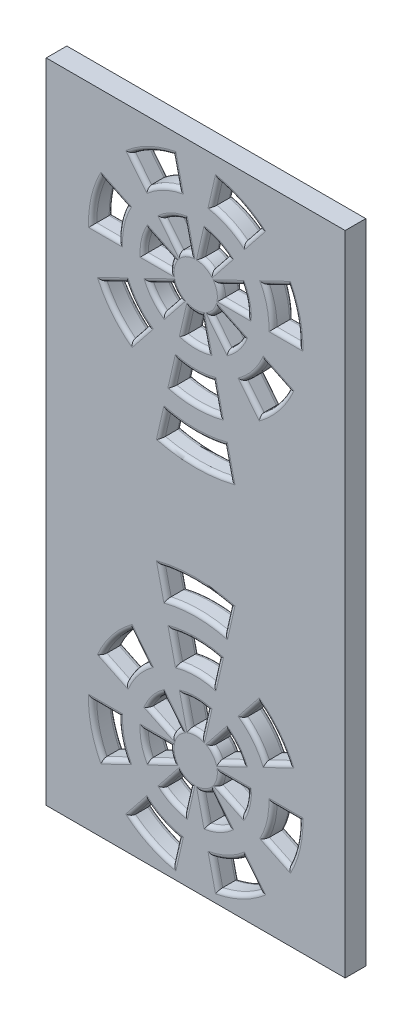
SolidWorks part; units mm, degrees
ref_plane "Front Plane" through (0, 0, 0) normal (0, 0, 1) x (1, 0, 0)
ref_plane "Top Plane" through (0, 0, 0) normal (0, 1, 0) x (1, 0, 0)
ref_plane "Right Plane" through (0, 0, 0) normal (1, 0, 0) x (0, 0, -1)
sketch "Sketch1" plane through (0, 0, 0) normal (0, 1, 0) x (1, 0, 0)
  line L1 (-19.5, 77.5) -> (19.5, 77.5)
  line L2 (-19.5, 77.5) -> (-19.5, -77.5)
  line L3 (-19.5, -77.5) -> (19.5, -77.5)
  line L4 (19.5, 77.5) -> (19.5, -77.5)
  line L5 (-19.5, 77.5) -> (19.5, -77.5) construction
  line L6 (-19.5, -77.5) -> (19.5, 77.5) construction
  point P0 (0, 0)
  dimension "D1" = 39
  dimension "D2" = 155
extrude "Boss-Extrude1" add sketch "Sketch1" along normal blind 2
sketch "Sketch2" plane through (0, 2, 0) normal (0, 1, 0) x (1, 0, 0)
  line L0 (-17.5, -75.5) -> (-17.5, -77.5)
  line L1 (-19.5, 77.5) -> (19.5, 77.5)
  line L2 (-19.5, 77.5) -> (-19.5, -77.5)
  line L3 (-19.5, -77.5) -> (19.5, -77.5)
  line L4 (19.5, 77.5) -> (19.5, -77.5)
  line L5 (-17.5, 75.5) -> (17.5, 75.5)
  line L6 (-17.5, 75.5) -> (-17.5, -75.5)
  line L7 (-17.5, -75.5) -> (17.5, -75.5)
  line L8 (17.5, 75.5) -> (17.5, -75.5)
  line L9 (-17.5, 75.5) -> (17.5, -75.5) construction
  line L10 (-17.5, -75.5) -> (17.5, 75.5) construction
  line L11 (17.5, -75.5) -> (17.5, -77.5)
  point P6 (0, 0)
  line M9 (19.5, -77.5) -> (19.5, 77.5)
  line M10 (19.5, 77.5) -> (-19.5, 77.5)
  line M11 (-19.5, 77.5) -> (-19.5, -77.5)
  line M12 (-19.5, -77.5) -> (19.5, -77.5)
  dimension "D1" = 2
  dimension "D2" = 2
extrude "Boss-Extrude2" add sketch "Sketch2" along normal blind 78 contours L8 L11 L3 L0 L6 L5 M9 M10 M11 M12 region at (-19.0983, 2, 76.5)
sketch "Sketch3" plane through (0, 2, 0) normal (0, 1, 0) x (1, 0, 0)
  line L0 (-17.5, 75.5) -> (-17.5, -77.5) construction
  line L1 (-17.5, -77.5) -> (-15.5, -77.5)
  line L2 (-17.5, -77.5) -> (-17.5, -75.5)
  line L3 (-17.5, -75.5) -> (-15.5, -75.5)
  line L4 (-15.5, -77.5) -> (-15.5, -75.5)
  line L5 (-17.5, -73.3) -> (-15.5, -73.3)
  line L6 (-17.5, -73.3) -> (-17.5, -71.3)
  line L7 (-17.5, -71.3) -> (-15.5, -71.3)
  line L8 (-15.5, -73.3) -> (-15.5, -71.3)
  line L9 (17.5, 75.5) -> (17.5, -77.5) construction
  line L10 (17.5, -77.5) -> (15.5, -77.5)
  line L11 (17.5, -77.5) -> (17.5, -75.5)
  line L12 (17.5, -75.5) -> (15.5, -75.5)
  line L13 (15.5, -77.5) -> (15.5, -75.5)
  line L14 (17.5, -73.3) -> (15.5, -73.3)
  line L15 (17.5, -73.3) -> (17.5, -71.3)
  line L16 (17.5, -71.3) -> (15.5, -71.3)
  line L17 (15.5, -73.3) -> (15.5, -71.3)
  line L18 (15.5, -75.5) -> (15.5, -73.3) construction
  line L19 (-15.5, -73.3) -> (15.5, -73.3) construction
  line L20 (-15.5, -75.5) -> (-15.5, -73.3) construction
  line L21 (-15.5, -75.5) -> (15.5, -75.5) construction
  line L22 (15.5, -71.3) -> (-15.5, -71.3) construction
  dimension "D1" = 2
  dimension "D2" = 2
  dimension "D3" = 2.2
  dimension "D4" = 2
extrude "Boss-Extrude3" add sketch "Sketch3" along normal up to surface (78 mm away) up to face at (0, 80, 0.5)
sketch "Sketch4" plane through (0, 0, -75.5) normal (0, 0, 1) x (1, 0, 0)
  line L0 (-17.5, 80) -> (-15.5, 80)
  line L1 (-17.5, 80) -> (17.5, 80) construction
  line L2 (-15.5, 80) -> (-15.5, 78)
  line L3 (-15.5, 78) -> (-17.5, 78)
  line L5 (-17.5, 78) -> (-17.5, 80)
  line L7 (-17.5, 80) -> (-17.5, 2) construction
  line L8 (-15.5, 73.8) -> (-17.5, 71.8)
  line L9 (-17.5, 71.8) -> (-17.5, 75.8)
  line L10 (-15.5, 73.8) -> (-15.5, 75.8)
  line L11 (-15.5, 75.8) -> (-17.5, 75.8)
  line L12 (0, 0) -> (0, 80) construction
  line L13 (15.5, 75.8) -> (17.5, 75.8)
  line L14 (15.5, 73.8) -> (15.5, 75.8)
  line L15 (17.5, 71.8) -> (17.5, 75.8)
  line L16 (15.5, 73.8) -> (17.5, 71.8)
  line L17 (17.5, 78) -> (17.5, 80)
  line L18 (15.5, 78) -> (17.5, 78)
  line L19 (15.5, 80) -> (15.5, 78)
  line L20 (17.5, 80) -> (15.5, 80)
  dimension "D1" = 2
  dimension "D2" = 2
  dimension "D3" = 45
  dimension "D4" = 2.2
  dimension "D5" = 2
extrude "Boss-Extrude4" add sketch "Sketch4" along normal up to surface (153 mm away) up to face at (0, 40.5, 77.5)
sketch "Sketch5" plane through (0, 2, 0) normal (0, 1, 0) x (1, 0, 0)
  line L1 (-15.5, -77.5) -> (15.5, -77.5)
  line L2 (-15.5, -77.5) -> (-15.5, -75.5)
  line L3 (-15.5, -75.5) -> (15.5, -75.5)
  line L4 (15.5, -77.5) -> (15.5, -75.5)
  line L5 (-15.5, -71.3) -> (15.5, -71.3)
  line L6 (-15.5, -71.3) -> (-15.5, -73.3)
  line L7 (-15.5, -73.3) -> (15.5, -73.3)
  line L8 (15.5, -71.3) -> (15.5, -73.3)
sketch "Sketch6" plane through (0, 0, -75.5) normal (0, 0, 1) x (1, 0, 0)
  line L0 (-17.5, 78) -> (-15.5, 78) construction
  line L1 (-17.5, 78) -> (17.5, 78)
  line L2 (-17.5, 78) -> (-17.5, 75.8)
  line L3 (-17.5, 75.8) -> (17.5, 75.8)
  line L4 (17.5, 78) -> (17.5, 75.8)
  line L5 (-17.5, 78) -> (-17.5, 75.8) construction
  line L6 (-15.5, 75.8) -> (-17.5, 75.8) construction
extrude "Cut-Extrude1" cut sketch "Sketch6" along normal through all
sketch "Sketch7" plane through (0, 2, 0) normal (0, 1, 0) x (1, 0, 0)
  line L1 (-17.5, -75.5) -> (17.5, -75.5)
  line L2 (-17.5, -75.5) -> (-17.5, -73.3)
  line L3 (-17.5, -73.3) -> (17.5, -73.3)
  line L4 (17.5, -75.5) -> (17.5, -73.3)
extrude "Cut-Extrude2" cut sketch "Sketch7" along normal through all
extrude "Boss-Extrude5" add sketch "Sketch5" along normal blind 2
sketch "Sketch8" plane through (0, 0, 0) normal (1, 0, 0) x (0, 0, -1)
  line L0 (75.5, 80) -> (73.5, 80)
  line L1 (-73.3, 80) -> (75.5, 80) construction
  line L2 (73.5, 80) -> (73.5, 78)
  line L3 (-73.3, 78) -> (75.5, 78) construction
  line L4 (73.5, 78) -> (75.5, 78)
  line L5 (75.5, 78) -> (75.5, 80)
  line L6 (75.5, 75.8) -> (73.5, 75.8)
  line L7 (-73.3, 75.8) -> (75.5, 75.8) construction
  line L8 (73.5, 75.8) -> (73.5, 73.8)
  line L9 (-71.3, 73.8) -> (75.5, 73.8) construction
  line L10 (73.5, 73.8) -> (75.5, 71.8)
  line L11 (75.5, 71.8) -> (75.5, 75.8)
  dimension "D1" = 2
extrude "Boss-Extrude6" add sketch "Sketch8" along normal up to surface and the other way up to surface up to face at (17.5, 36.9, -2.1) other way up to face at (-17.5, 36.9, -2.1)
sketch "Sketch10" plane through (-17.5, 0, 0) normal (1, 0, 0) x (0, 0, -1)
  line L1 (-75.5, 75.8) -> (-77.5, 75.8)
  line L2 (-75.5, 75.8) -> (-75.5, 78)
  line L3 (-75.5, 78) -> (-77.5, 78)
  line L4 (-77.5, 75.8) -> (-77.5, 78)
  line L5 (-73.3, 80) -> (-75.5, 80)
  line L6 (-73.3, 80) -> (-73.3, 78)
  line L7 (-73.3, 78) -> (-75.5, 78)
  line L8 (-75.5, 80) -> (-75.5, 78)
  line M1 (-75.5, 80) -> (-75.5, 78)
  line M2 (-75.5, 78) -> (-77.5, 78)
  line M3 (-77.5, 78) -> (-77.5, 75.8)
  line M4 (-77.5, 75.8) -> (-75.5, 75.8)
  line M11 (-73.3, 78) -> (-73.3, 80)
  line M12 (-73.3, 80) -> (-75.5, 80)
extrude "Boss-Extrude8" add sketch "Sketch10" along normal up to surface (2 mm away) contours L2 M4 M2 M3 | L7 M11 M12 M1 region at (-17.5, 79, 74.4) region at (-17.5, 76.9, 76.5) up to face at (-15.5, 79, -0.1)
sketch "Sketch11" plane through (17.5, 0, 0) normal (-1, 0, 0) x (0, 0, 1)
  line L1 (75.5, 75.8) -> (77.5, 75.8)
  line L2 (75.5, 75.8) -> (75.5, 78)
  line L3 (75.5, 78) -> (77.5, 78)
  line L4 (77.5, 75.8) -> (77.5, 78)
  line L5 (73.3, 80) -> (75.5, 80)
  line L6 (73.3, 80) -> (73.3, 78)
  line L7 (73.3, 78) -> (75.5, 78)
  line L8 (75.5, 80) -> (75.5, 78)
  line M2 (75.5, 75.8) -> (77.5, 75.8)
  line M3 (77.5, 75.8) -> (77.5, 78)
  line M4 (77.5, 78) -> (75.5, 78)
  line M5 (75.5, 78) -> (75.5, 80)
  line M6 (75.5, 80) -> (73.3, 80)
  line M7 (73.3, 80) -> (73.3, 78)
extrude "Boss-Extrude9" add sketch "Sketch11" along normal up to surface (2 mm away) contours L2 M2 M3 M4 | L7 M7 M5 M6 region at (17.5, 76.9, 76.5) region at (17.5, 79, 74.4) up to face at (15.5, 79, -0.1)
fillet "Fillet2" radius 2.5 17 edges at (-17.5, 36.9, 71.3) (17.5, 36.9, 71.3) (19.5, 40, 77.5) (-19.5, 40, 77.5) (-19.5, 40, -77.5) (-17.5, 36.9, -75.5) (17.5, 36.9, -75.5) (19.5, 40, -77.5) (-19.5, 80, 0) (0, 80, -77.5) (19.5, 80, 0) (0, 0, -77.5) (0, 0, 77.5) (-19.5, 0, 0) (19.5, 0, 0) (-17.5, 80, 77.5) (17.5, 80, 77.5)
sketch "Sketch13" plane through (0, 0, -77.5) normal (0, 0, -1) x (-1, 0, 0)
  line L0 (15.5, 77.5) -> (15.5, 4) construction
  line L1 (-15.5, 7) -> (15.5, 7)
  line L2 (-15.5, 7) -> (-15.5, 4)
  line L3 (-15.5, 4) -> (15.5, 4)
  line L4 (15.5, 7) -> (15.5, 4)
  dimension "D1" = 3
sketch "Sketch14" plane through (0, 0, -75.5) normal (0, 0, 1) x (1, 0, 0)
  line L1 (-18.25, 9) -> (18.25, 9)
  line L2 (-18.25, 9) -> (-18.25, 1.25)
  line L3 (-18.25, 1.25) -> (18.25, 1.25)
  line L4 (18.25, 9) -> (18.25, 1.25)
  line L5 (15.5, 7) -> (-15.5, 7) construction
  line L7 (17, 0) -> (17, 2.5) construction
  line L8 (19.5, 2.5) -> (17, 2.5) construction
  line L10 (-19.5, 2.5) -> (-17, 2.5) construction
  point P20 (17, 1.25)
  point P23 (18.25, 2.5)
  point P26 (-18.25, 2.5)
  dimension "D1" = 2
extrude "Boss-Extrude10" add sketch "Sketch14" along normal blind 2
extrude "Cut-Extrude4" cut sketch "Sketch13" against normal blind 2
fillet "Fillet3" radius 2 1 edges at (0, 9, -73.5)
fillet "Fillet4" radius 0.5 12 edges at (0, 4, -77.5) (0, 7, -77.5) (15.5, 7, -76.5) (15.5, 4, -76.5) (15.5, 5.5, -77.5) (-15.5, 4, -76.5) (-15.5, 7, -76.5) (-15.5, 5.5, -77.5) (0, 7, -75.5) (-15.5, 5.5, -75.5) (0, 4, -75.5) (15.5, 5.5, -75.5)
sketch "Sketch15" plane through (0, 0, 0) normal (0, -1, 0) x (1, 0, 0)
  line L0 (0, 77.5) -> (0, 0) construction
  line L1 (-17, 77.5) -> (17, 77.5) construction
  line L2 (0, 0) -> (0, -77.5) construction
  line L4 (17, -77.5) -> (-17, -77.5) construction
  circle A0 centre (0, 38.75) radius 5.1
  circle A1 centre (0, -38.75) radius 5.1
  dimension "D1" = 10.2
extrude "Cut-Extrude5" cut sketch "Sketch15" against normal through all
sketch "Sketch16" plane through (0, 2, 0) normal (0, 1, 0) x (1, 0, 0)
  circle A0 centre (0, 38.75) radius 7.1
  circle A1 centre (0, -38.75) radius 7.1
  circle A2 centre (0, 38.75) radius 5.1 construction
  dimension "D1" = 2
extrude "Boss-Extrude11" add sketch "Sketch16" along normal blind 1
fillet "Fillet5" radius 0.5 4 edges at (0, 2, 45.85) (0, 2, -31.65) (0, 3, 45.85) (0, 3, -31.65)
sketch "Sketch12" plane through (0, 0, -75.5) normal (0, 0, 1) x (1, 0, 0)
  line L0 (0, 0) -> (0, 40) construction
  line L2 (0, 20) -> (-20, 20)
  line L3 (0, 20) -> (-18.0194, 11.3223)
  line L4 (0, 20) -> (-12.4698, 4.3634)
  line L5 (0, 20) -> (-4.4504, 0.5014)
  line L6 (0, 20) -> (4.4504, 0.5014)
  line L7 (0, 20) -> (12.4698, 4.3634)
  line L8 (0, 20) -> (18.0194, 11.3223)
  line L9 (0, 20) -> (20, 20)
  line L10 (0, 20) -> (18.0194, 28.6777)
  line L11 (0, 20) -> (12.4698, 35.6366)
  line L12 (0, 20) -> (4.4504, 39.4986)
  line L13 (0, 20) -> (-4.4504, 39.4986)
  line L14 (0, 20) -> (-12.4698, 35.6366)
  line L15 (0, 20) -> (-18.0194, 28.6777)
  line L16 (0, 40) -> (0, 80) construction
  line L17 (15.5, 80) -> (-15.5, 80) construction
  circle A0 centre (0, 20) radius 10
  circle A1 centre (0, 20) radius 7.5
  circle A2 centre (0, 20) radius 5
  circle A3 centre (0, 20) radius 2.5
  circle A4 centre (0, 20) radius 12.5
  circle A5 centre (0, 20) radius 15
  circle A6 centre (0, 20) radius 17.5
  circle A7 centre (0, 20) radius 20
  point P26 (0, 20)
  dimension "D1" = 20
  dimension "D2" = 2.5
  dimension "D3" = 2.5
  dimension "D4" = 2.5
  dimension "D6" = 2.5
  dimension "D7" = 2.5
  dimension "D8" = 2.5
  dimension "D9" = 2.5
  dimension "D5" = 14
extrude "Cut-Extrude6" cut sketch "Sketch12" against normal blind 10 contours A3 L12 A2 L13 | A3 L10 A2 L11 | A3 L8 A2 L9 | A3 L6 A2 L7 | A3 L4 A2 L5 | A3 L2 A2 L3 | A3 L14 A2 L15 | A1 L12 A0 L13 | A1 L10 A0 L11 | A1 L8 A0 L9 | A1 L6 A0 L7 | A1 L4 A0 L5 | A1 L2 A0 L3 | A1 L14 A0 L15 | L12 A5 L13 A4 region at (-3.7596, 19.1419, -75.5) region at (-1.6732, 16.5256, -75.5) region at (1.6732, 16.5256, -75.5) region at (3.7596, 19.1419, -75.5) region at (3.015, 22.4044, -75.5) region at (0, 23.8563, -75.5) region at (-3.015, 22.4044, -75.5) region at (-8.5168, 18.0561, -75.5) region at (-3.7903, 12.1293, -75.5) region at (3.7903, 12.1293, -75.5) region at (8.5168, 18.0561, -75.5) region at (6.8299, 25.4467, -75.5) region at (0, 28.7358, -75.5) region at (-6.8299, 25.4467, -75.5) region at (0, 33.6725, -75.5)
fillet "Fillet6" radius 0.4 120 edges at (-3.3786, 18.3729, -77.5) (-4.8746, 18.8874, -77.5) (-3.75, 20, -77.5) (-2.4373, 19.4437, -77.5) (0, 30, -77.5) (1.9471, 28.5306, -77.5) (0, 27.5, -77.5) (2.3381, 22.9319, -77.5) (3.9092, 23.1174, -77.5) (2.3381, 17.0681, -77.5) (1.0847, 17.7476, -77.5) (8.75, 20, -77.5) (9.7493, 17.7748, -77.5) (7.8835, 16.2035, -77.5) (7.312, 18.3311, -77.5) (-4.3388, 10.9903, -77.5) (-3.2541, 13.2427, -77.5) (-7.8835, 23.7965, -77.5) (-5.4555, 26.841, -77.5) (-5.8637, 24.6762, -77.5) (0, 35, -77.5) (3.0597, 33.4053, -77.5) (0, 32.5, -77.5) (0.8345, 23.656, -77.5) (0, 22.5, -77.5) (-9.7493, 17.7748, -77.5) (5.4555, 13.159, -77.5) (4.3388, 10.9903, -77.5) (1.9471, 11.4694, -77.5) (-0.8345, 16.344, -77.5) (-2.1694, 15.4952, -77.5) (-2.3381, 17.0681, -77.5) (-1.0847, 17.7476, -77.5) (3.75, 20, -77.5) (4.8746, 18.8874, -77.5) (3.3786, 18.3729, -77.5) (2.4373, 19.4437, -77.5) (7.8183, 26.2349, -77.5) (-3.9092, 23.1174, -77.5) (-1.9546, 21.5587, -77.5) (-3.0597, 33.4053, -77.5) (-3.3786, 18.3729, -75.5) (-2.4373, 19.4437, -75.5) (0, 30, -75.5) (-1.9471, 28.5306, -75.5) (0, 27.5, -75.5) (3.3786, 21.6271, -75.5) (1.9546, 21.5587, -75.5) (0.8345, 16.344, -75.5) (2.1694, 15.4952, -75.5) (2.3381, 17.0681, -75.5) (7.8835, 16.2035, -75.5) (9.7493, 17.7748, -75.5) (7.312, 18.3311, -75.5) (-4.3388, 10.9903, -75.5) (-7.8183, 26.2349, -75.5) (-7.8835, 23.7965, -75.5) (-5.8637, 24.6762, -75.5) (0, 32.5, -75.5) (3.0597, 33.4053, -75.5) (0, 35, -75.5) (0.8345, 23.656, -75.5) (0, 25, -75.5) (-0.8345, 23.656, -75.5) (0, 22.5, -75.5) (-9.7493, 17.7748, -75.5) (-7.8835, 16.2035, -75.5) (-7.312, 18.3311, -75.5) (1.9471, 11.4694, -75.5) (5.4555, 13.159, -75.5) (3.2541, 13.2427, -75.5) (-2.3381, 17.0681, -75.5) (-2.1694, 15.4952, -75.5) (-0.8345, 16.344, -75.5) (-1.0847, 17.7476, -75.5) (3.3786, 18.3729, -75.5) (3.75, 20, -75.5) (2.4373, 19.4437, -75.5) (7.8835, 23.7965, -75.5) (5.4555, 26.841, -75.5) (5.8637, 24.6762, -75.5) (-3.3786, 21.6271, -75.5) (-1.9546, 21.5587, -75.5) (1.9471, 28.5306, -75.5) (-1.9471, 28.5306, -77.5) (3.3786, 21.6271, -77.5) (1.9546, 21.5587, -77.5) (2.1694, 15.4952, -77.5) (0.8345, 16.344, -77.5) (-1.9471, 11.4694, -77.5) (-5.4555, 13.159, -77.5) (-7.8183, 26.2349, -77.5) (-0.8345, 23.656, -77.5) (0, 25, -77.5) (-7.8835, 16.2035, -77.5) (-8.75, 20, -77.5) (-7.312, 18.3311, -77.5) (3.2541, 13.2427, -77.5) (5.4555, 26.841, -77.5) (7.8835, 23.7965, -77.5) (5.8637, 24.6762, -77.5) (-3.3786, 21.6271, -77.5) (-2.3381, 22.9319, -77.5) (-3.75, 20, -75.5) (-4.8746, 18.8874, -75.5) (3.9092, 23.1174, -75.5) (2.3381, 22.9319, -75.5) (1.0847, 17.7476, -75.5) (8.75, 20, -75.5) (-5.4555, 13.159, -75.5) (-1.9471, 11.4694, -75.5) (-3.2541, 13.2427, -75.5) (-5.4555, 26.841, -75.5) (-3.0597, 33.4053, -75.5) (-8.75, 20, -75.5) (4.3388, 10.9903, -75.5) (4.8746, 18.8874, -75.5) (7.8183, 26.2349, -75.5) (-2.3381, 22.9319, -75.5) (-3.9092, 23.1174, -75.5)
ref_plane "Plane1" through (0, 40, 0) normal (0, 1, 0) x (1, 0, 0)
mirror "Mirror1" about plane through (0, 40, 0) normal (0, 1, 0) of "Fillet6", "Cut-Extrude6"
fillet "Fillet7" radius 0.5 8 edges at (15.5, 80, 0.75) (15.5, 79.2678, 76.7678) (-15.5, 80, 0.75) (-15.5, 79.2678, 76.7678) (0, 80, -73.5) (0, 4, 77.5) (15.5, 40.75, 77.5) (-15.5, 40.75, 77.5)
sketch "Sketch17" plane through (0, 0, 0) normal (0, 0, 1) x (1, 0, 0)
  line L0 (-16, 80) -> (16, 80) construction
  line L1 (-14.5, 80) -> (14.5, 80)
  line L2 (-14.5, 80) -> (-14.5, 9)
  line L3 (-14.5, 9) -> (14.5, 9)
  line L4 (14.5, 80) -> (14.5, 9)
  line L5 (15, 9) -> (-15, 9) construction
  line L6 (0, 0) -> (0, 9) construction
  line L8 (19.5, 77.5) -> (19.5, 2.5) construction
  line L9 (-19.5, 80) -> (19.5, 80)
  line L10 (-19.5, 80) -> (-19.5, 0)
  line L11 (-19.5, 0) -> (19.5, 0)
  line L12 (19.5, 80) -> (19.5, 0)
  line L13 (-19.5, 2.5) -> (-19.5, 77.5) construction
  line L14 (17, 0) -> (-17, 0) construction
  dimension "D1" = 29
extrude "Cut-Extrude7" cut sketch "Sketch17" against normal through all both and the other way through all contours L6 L11 L12 L9 L4 L3 | L11 L6 L3 L2 L9 L10 region at (-14.6016, 31.2672, 0) region at (14.6016, 31.2672, 0)
sketch "Sketch18" plane through (0, 0, -75.5) normal (0, 0, 1) x (1, 0, 0)
  line L1 (-14.5, 71.8) -> (14.5, 71.8)
  line L2 (-14.5, 71.8) -> (-14.5, 80)
  line L3 (-14.5, 80) -> (14.5, 80)
  line L4 (14.5, 71.8) -> (14.5, 80)
extrude "Cut-Extrude8" cut sketch "Sketch18" against normal through all both and the other way through all
